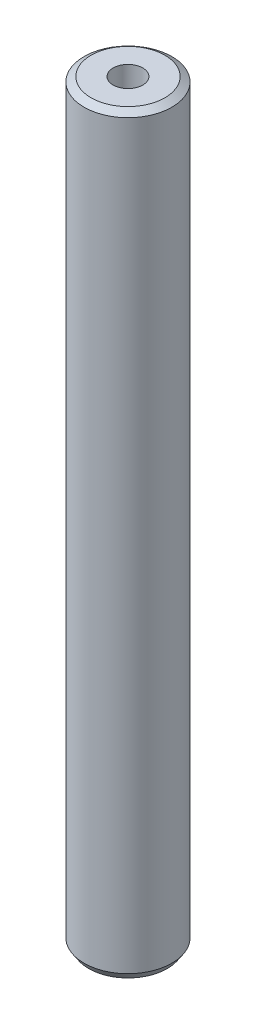
SolidWorks part; units mm, degrees
ref_plane "Front Plane" through (0, 0, 0) normal (0, 0, 1) x (1, 0, 0)
ref_plane "Top Plane" through (0, 0, 0) normal (0, 1, 0) x (1, 0, 0)
ref_plane "Right Plane" through (0, 0, 0) normal (1, 0, 0) x (0, 0, -1)
sketch "Sketch1" plane through (0, 0, 0) normal (0, 1, 0) x (1, 0, 0)
  circle A0 centre (0, 0) radius 35
  dimension "SHAFT_OD" = 70
extrude "Boss-Extrude1" add sketch "Sketch1" along normal blind 600
sketch "Sketch2" plane through (0, 0, 0) normal (0, 1, 0) x (1, 0, 0)
  circle A0 centre (0, 0) radius 11.815
  dimension "BORE_D" = 23.63
extrude "Cut-Extrude1" cut sketch "Sketch2" along normal through all
chamfer "Chamfer1" distance 3.7016 angle 56.487 2 edges at (0, 600, 35) (0, 0, 35) first distance on face at (0, 600, 35) first distance on face at (0, 0, 11.815)
